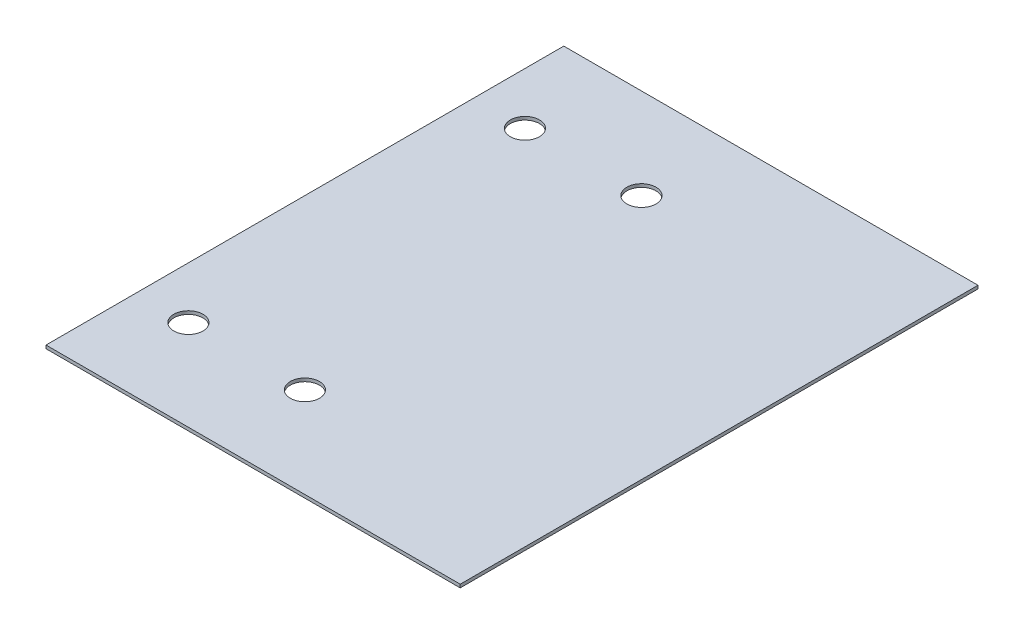
SolidWorks part; units mm, degrees
ref_plane "Front Plane" through (0, 0, 0) normal (0, 0, 1) x (1, 0, 0)
ref_plane "Top Plane" through (0, 0, 0) normal (0, 1, 0) x (1, 0, 0)
ref_plane "Right Plane" through (0, 0, 0) normal (1, 0, 0) x (0, 0, -1)
sketch "Sketch1" plane through (0, 0, 0) normal (0, 1, 0) x (1, 0, 0)
  line L1 (0, 0) -> (406.4, 0)
  line L2 (0, 0) -> (0, 508)
  line L3 (0, 508) -> (406.4, 508)
  line L4 (406.4, 0) -> (406.4, 508)
  dimension "D1" = 406.4
  dimension "D2" = 508
extrude "Boss-Extrude1" add sketch "Sketch1" along normal blind 3.175
sketch "Sketch2" plane through (0, 3.175, 0) normal (0, 1, 0) x (1, 0, 0)
  line L0 (107.95, 419.1) -> (107.95, 508) construction
  line L1 (50.8, 419.1) -> (165.1, 419.1) construction
  line L3 (50.8, 88.9) -> (165.1, 88.9) construction
  line L5 (406.4, 508) -> (0, 508) construction
  line L6 (107.95, 88.9) -> (107.95, 0) construction
  line L7 (0, 0) -> (406.4, 0) construction
  line L9 (0, 508) -> (0, 0) construction
  circle A0 centre (50.8, 419.1) radius 14.2875
  circle A1 centre (165.1, 419.1) radius 14.2875
  circle A2 centre (50.8, 88.9) radius 14.2875
  circle A3 centre (165.1, 88.9) radius 14.2875
  dimension "D1" = 28.575
  dimension "D2" = 28.575
  dimension "D3" = 28.575
  dimension "D4" = 28.575
  dimension "D5" = 114.3
  dimension "D6" = 114.3
  dimension "D7" = 330.2
  dimension "D8" = 50.8
extrude "Cut-Extrude1" cut sketch "Sketch2" against normal blind 3.175
